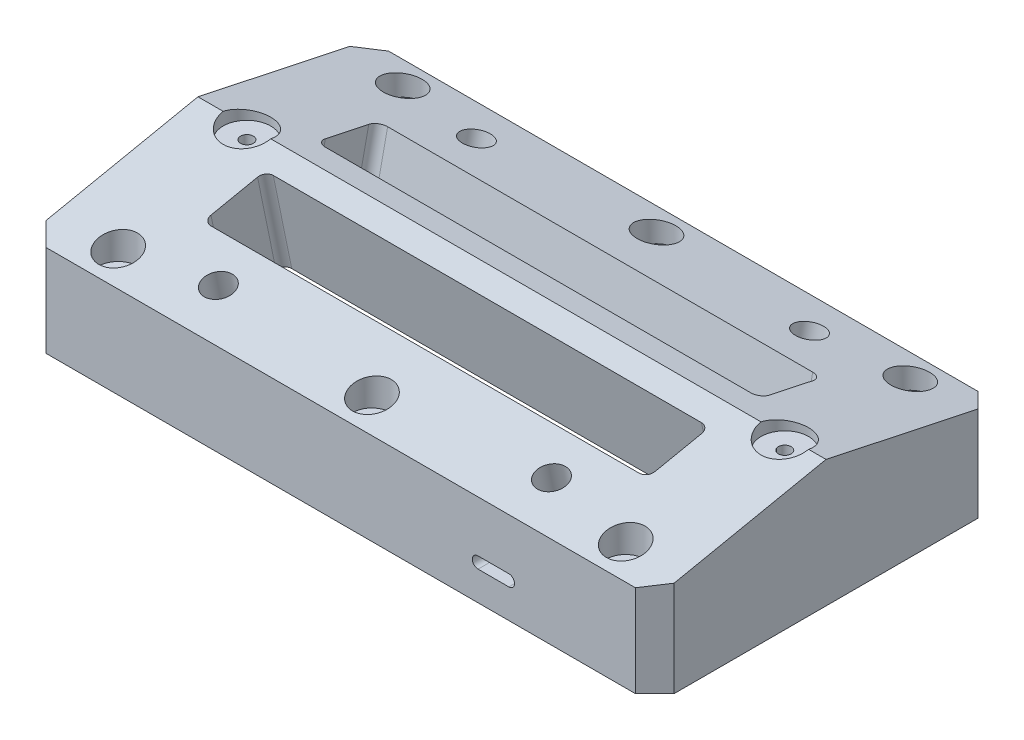
SolidWorks part; units mm, degrees
material "Custom Plastic"
ref_plane "Front Plane" through (0, 0, 0) normal (0, 0, 1) x (1, 0, 0)
ref_plane "Top Plane" through (0, 0, 0) normal (0, 1, 0) x (1, 0, 0)
ref_plane "Right Plane" through (0, 0, 0) normal (1, 0, 0) x (0, 0, -1)
sketch "Sketch1" plane through (0, 0, 0) normal (0, 1, 0) x (1, 0, 0)
  line L1 (0, 0) -> (198, 0)
  line L2 (0, 0) -> (0, 108)
  line L3 (0, 108) -> (198, 108)
  line L4 (198, 0) -> (198, 108)
  dimension "D1" = 198
  dimension "D2" = 108
extrude "Boss-Extrude1" add sketch "Sketch1" along normal blind 40
ref_plane "Left" through (198, 0, 0) normal (1, 0, 0) x (0, 0, -1)
ref_plane "Bot" through (0, 40, 0) normal (0, 1, 0) x (1, 0, 0)
ref_plane "der loco" through (0, 0, -52) normal (0, 0, -1) x (-1, 0, 0)
sketch "Sketch4" plane through (0, 0, 0) normal (0, 1, 0) x (1, 0, 0)
  line L0 (0, 108) -> (0, 0) construction
  line L1 (8.5, 31.5) -> (189.5, 31.5)
  line L2 (8.5, 31.5) -> (8.5, 76.5)
  line L3 (8.5, 76.5) -> (189.5, 76.5)
  line L4 (189.5, 31.5) -> (189.5, 76.5)
  line L5 (0, 0) -> (198, 0) construction
  dimension "D1" = 181
  dimension "D2" = 8.5
  dimension "D3" = 45
  dimension "D4" = 31.5
extrude "Cut-Extrude2" cut sketch "Sketch4" along normal blind 10 contours L2 L1 L4 L3
ref_plane "Plane32" through (0, 10, 0) normal (0, -1, 0) x (-1, 0, 0)
sketch "Sketch5" plane through (198, 0, 0) normal (1, 0, 0) x (0, 0, -1)
  line L0 (54, 40) -> (108, 28.5219)
  line L1 (0, 40) -> (108, 40) construction
  line L2 (108, 28.5219) -> (108, 40)
  line L3 (108, 40) -> (54, 40)
  line L4 (108, 40) -> (108, 0) construction
  dimension "D1" = 12
  dimension "D2" = 54
extrude "Cut-Extrude3" cut sketch "Sketch5" against normal blind 175
ref_plane "Plane24" through (0, 10, 0) normal (0, -1, 0) x (-1, 0, 0)
sketch "Sketch53" plane through (0, 10, 0) normal (0, -1, 0) x (-1, 0, 0)
  line L0 (-8.5, 51.5) -> (-8.5, 31.5)
  line L1 (-8.5, 76.5) -> (-8.5, 31.5) construction
  line L2 (-8.5, 31.5) -> (-39.5, 31.5)
  line L3 (-8.5, 31.5) -> (-189.5, 31.5) construction
  line L4 (-39.5, 31.5) -> (-8.5, 51.5)
  line L5 (-8.5, 54) -> (-189.5, 54) construction
  line L6 (-189.5, 31.5) -> (-189.5, 76.5) construction
  line L7 (-8.5, 56.5) -> (-8.5, 76.5)
  line L8 (-8.5, 76.5) -> (-39.5, 76.5)
  line L9 (-39.5, 76.5) -> (-8.5, 56.5)
  line L10 (-99, 76.5) -> (-99, 31.5) construction
  line L11 (-8.5, 76.5) -> (-189.5, 76.5) construction
  line L12 (-8.5, 31.5) -> (-189.5, 31.5) construction
  line L13 (-158.5, 76.5) -> (-189.5, 56.5)
  line L14 (-189.5, 76.5) -> (-158.5, 76.5)
  line L15 (-189.5, 56.5) -> (-189.5, 76.5)
  line L16 (-158.5, 31.5) -> (-189.5, 51.5)
  line L17 (-189.5, 31.5) -> (-158.5, 31.5)
  line L18 (-189.5, 51.5) -> (-189.5, 31.5)
  dimension "D1" = 31
  dimension "D2" = 20
extrude "Boss-Extrude11" add sketch "Sketch53" along normal up to surface (10 mm away) up to face at (99, 0, -54)
ref_plane "izq loco" through (0, 0, -57) normal (0, 0, -1) x (-1, 0, 0)
sketch "Sketch18" plane through (198, 0, 0) normal (1, 0, 0) x (0, 0, -1)
  line L0 (0, 28.9154) -> (0, 40)
  line L1 (0, 40) -> (0, 0) construction
  line L2 (0, 40) -> (54, 40)
  line L3 (54, 40) -> (0, 28.9154)
  line L4 (0, 40) -> (54, 40) construction
  line L5 (40.01, 37.1283) -> (56.6571, -43.9699) construction
  line L6 (54, -44.525) -> (24.4749, -50.6931) construction
  line L7 (0, 28.9154) -> (54, 28.9154) construction
  line L8 (54, 28.9154) -> (54, 40) construction
  line L9 (54, 28.9154) -> (108, 28.9154) construction
  line L10 (108, 28.5219) -> (108, 0) construction
  dimension "D1" = 54
  dimension "D2" = 11.6
  dimension "D3" = 13.99
  dimension "D4" = 11.6
extrude "Cut-Extrude12" cut sketch "Sketch18" against normal up to surface (175 mm away) up to face at (23, 36.174, -90)
sketch "Sketch60" plane through (0, 0, 0) normal (0, 1, 0) x (1, 0, 0)
  point P0 (8.5, 31.5)
  point P1 (39.5, 31.5)
  point P2 (8.5, 76.5)
  point P6 (39.5, 76.5)
  dimension "D1" = 20
  dimension "D2" = 31
  dimension "D3" = 20
  dimension "D4" = 31
ref_axis "Axis6" through (8.5, 0, -31.5) along (1, 0, 0)
sketch "Sketch69" plane through (0, 10, 0) normal (0, -1, 0) x (-1, 0, 0)
  point P0 (-39.5, 56.5)
  point P1 (-8.5, 51.5)
  point P2 (-38.5, 51.5)
  point P3 (-8.5, 56.5)
  dimension "D1" = 31
  dimension "D2" = 20
  dimension "D3" = 20
  dimension "D4" = 30
sketch "der loco axis" plane through (0, 0, -52) normal (0, 0, -1) x (-1, 0, 0)
  point P0 (-8.5, 8.5)
  point P1 (-38.5, 8.5)
  dimension "D1" = 1.5
sketch "izq loco axis" plane through (0, 0, -57) normal (0, 0, -1) x (-1, 0, 0)
  line L0 (-39.5, 0) -> (-39.5, 10) construction
  line L1 (-8.5, 0) -> (-8.5, 10) construction
  point P0 (-8.5, 8.4959)
  point P1 (-39.5, 8.4959)
  dimension "D1" = 1.5041
ref_plane "Plane3" through (0, 49.2528, -10.469) normal (0, 0.9781, -0.2079) x (1, 0, 0)
ref_axis "Axis8" through (39.5, 0, -76.5) along (-1, 0, 0)
ref_axis "Axis9" through (8.5, 8.4959, -57) along (1, 0, 0)
ref_axis "Axis10" through (38.5, 8.5, -52) along (-1, 0, 0)
ref_plane "Izq bueno" through (0, 28.0127, -12.2048) normal (0, 0.9168, -0.3994) x (1, 0, 0)
sketch "Izq" plane through (0, 28.0127, -12.2048) normal (0, 0.9168, -0.3994) x (1, 0, 0)
  line L0 (8.5, 48.8622) -> (29.5, 70.1326)
  line L1 (29.5, 70.1326) -> (8.5, 70.1326)
  line L2 (8.5, 70.1326) -> (8.5, 48.8622)
  dimension "D1" = 21
extrude "Cut-Extrude28" cut sketch "Izq" against normal blind 14.5
ref_plane "Der bueno" through (0, -11.1449, -4.6211) normal (0, 0.9237, 0.383) x (1, 0, 0)
sketch "Der" plane through (0, -11.1449, -4.6211) normal (0, 0.9237, 0.383) x (1, 0, 0)
  line L0 (8.5, 51.2902) -> (29.5, 29.0979)
  line L1 (29.5, 29.0979) -> (8.5, 29.0979)
  line L2 (8.5, 29.0979) -> (8.5, 51.2902)
  dimension "D1" = 21
extrude "Cut-Extrude29" cut sketch "Der" against normal blind 14.5
sketch "Sketch97" plane through (0, 0, 0) normal (0, 1, 0) x (1, 0, 0)
  line L0 (8.5, 57.5) -> (29.5, 76.5)
  line L1 (29.5, 76.5) -> (158.5, 76.5)
  line L3 (158.5, 31.5) -> (29.5, 31.5)
  line L4 (29.5, 31.5) -> (8.5, 51.5)
  line L5 (8.5, 51.5) -> (8.5, 57.5)
  line L7 (158.5, 76.5) -> (189.5, 56.5)
  line L8 (189.5, 56.5) -> (189.5, 51.5)
  line L9 (189.5, 51.5) -> (158.5, 31.5)
  line L10 (39.5, 76.5) -> (158.5, 76.5) construction
  dimension "D1" = 6
extrude "Cut-Extrude40" cut sketch "Sketch97" along normal up to surface (10 mm away) up to face at (99, 10, -54)
ref_axis "Axis11" through (99, 0, -108) along (0, 0, 1)
ref_plane "Plane33" through (99, 0, 0) normal (1, 0, 0) x (0, 0, -1)
mirror "Mirror2" about plane through (99, 0, 0) normal (1, 0, 0) of "Cut-Extrude29", "Cut-Extrude40", "Cut-Extrude28"
sketch "Sketch6" plane through (0, 49.2528, -10.469) normal (0, 0.9781, -0.2079) x (1, 0, 0)
  line L1 (32.2, 72.7099) -> (166.2, 72.7099)
  line L2 (29.2, 69.7099) -> (29.2, 55.7099)
  line L3 (32.2, 52.7099) -> (166.2, 52.7099)
  line L4 (169.2, 69.7099) -> (169.2, 55.7099)
  line L6 (23, 99.7099) -> (198, 99.7099) construction
  line L13 (198, 44.5035) -> (198, 99.7099) construction
  arc A0 (166.2, 72.7099) -> (169.2, 69.7099) centre (166.2, 69.7099) cw
  arc A1 (166.2, 52.7099) -> (169.2, 55.7099) centre (166.2, 55.7099) ccw
  arc A2 (29.2, 55.7099) -> (32.2, 52.7099) centre (32.2, 55.7099) ccw
  arc A3 (32.2, 72.7099) -> (29.2, 69.7099) centre (32.2, 69.7099) ccw
  point P14 (0, 0)
  point P15 (0, 0)
  point P18 (0, 0)
  dimension "D1" = 3
  dimension "D5" = 27
  dimension "D2" = 140
  dimension "D3" = 20
  dimension "D4" = 28.8
sketch "Sketch7" plane through (0, 0, 0) normal (1, 0, 0) x (0, 0, -1)
  line L1 (108, 40) -> (108, 0) construction
  line L2 (108, 40) -> (0, 40) construction
  line L3 (108, 40) -> (108, 35)
  line L5 (108, 35) -> (83.5051, 40)
  line L6 (108, 40) -> (83.5051, 40)
  line L7 (0, 35) -> (0, 40)
  line L8 (0, 40) -> (0, 0) construction
  line L9 (0, 40) -> (24.4949, 40)
  line L10 (24.4949, 40) -> (0, 35)
  dimension "D1" = 25
  dimension "D2" = 35
  dimension "D3" = 35
  dimension "D4" = 25
extrude "Cut-Extrude5" cut sketch "Sketch7" along normal up to vertex (23 mm away) up to point (23, 40, 0)
sketch "Sketch9" plane through (0, 40, 0) normal (0, 1, 0) x (1, 0, 0)
  line L0 (0, 83.5051) -> (0, 24.4949) construction
  circle A0 centre (15.45, 54) radius 8
  point P6 (0, 54)
  dimension "D1" = 16
  dimension "D2" = 15.45
sketch "Sketch12" plane through (0, 40, 0) normal (0, 1, 0) x (1, 0, 0)
  line L0 (0, 83.5051) -> (0, 108) construction
  line L2 (23, 108) -> (0, 108) construction
  line L3 (23, 0) -> (0, 0) construction
  circle A0 centre (19.7, 98.85) radius 3.15
  circle A1 centre (99.7, 9.15) radius 3.15
  circle A2 centre (179.7, 9.15) radius 3.15
  circle A3 centre (19.7, 9.15) radius 3.15
  circle A4 centre (99.7, 98.85) radius 3.15
  circle A5 centre (179.7, 98.85) radius 3.15
  dimension "D2" = 6.3
  dimension "D3" = 19.7
  dimension "D7" = 80
  dimension "D9" = 80
  dimension "D10" = 9.15
  dimension "D11" = 9.15
extrude "Cut-Extrude9" cut sketch "Sketch12" against normal through all
sketch "Sketch13" plane through (0, 49.2528, -10.469) normal (0, 0.9781, -0.2079) x (1, 0, 0)
  line L0 (23, 44.5035) -> (23, 99.7099) construction
  line L1 (23, 99.7099) -> (198, 99.7099) construction
  line L2 (198, 44.5035) -> (198, 99.7099) construction
  circle A0 centre (46.5, 86.7099) radius 4.5
  circle A1 centre (151.5, 86.7099) radius 4.5
  dimension "D1" = 9
  dimension "D4" = 9
  dimension "D2" = 23.5
  dimension "D3" = 13
  dimension "D5" = 46.5
extrude "Cut-Extrude10" cut sketch "Sketch13" against normal blind 16.5
ref_plane "Plane8" through (0, 33.6, 6.8586) normal (0, 0.9798, 0.2) x (1, 0, 0)
sketch "Sketch14" plane through (0, 27.1558, 8.572) normal (0, 0.9796, 0.2011) x (1, 0, 0)
  line L0 (23, 9.9742) -> (0, 9.9742) construction
  line L1 (23, 63.8767) -> (23, 114.4658) construction
  line L2 (198, 9.9742) -> (198, 34.9742) construction
  circle A0 centre (46.5, 22.9742) radius 4.5
  circle A1 centre (151.5, 22.9742) radius 4.5
  dimension "D1" = 9
  dimension "D2" = 9
  dimension "D3" = 13
  dimension "D4" = 23.5
  dimension "D5" = 46.5
extrude "Cut-Extrude11" cut sketch "Sketch14" against normal blind 16.5
ref_plane "Plane9" through (0, 27.7463, 5.6955) normal (0, 0.9796, 0.2011) x (1, 0, 0)
sketch "Sketch23" plane through (0, 27.7463, 5.6955) normal (0, 0.9796, 0.2011) x (1, 0, 0)
  line L0 (23, 60.9402) -> (198, 60.9402) construction
  line L1 (28.9, 60.1402) -> (169.5, 60.1402)
  line L2 (25.9, 57.1402) -> (25.9, 36.5402)
  line L3 (28.9, 33.5402) -> (169.5, 33.5402)
  line L4 (172.5, 57.1402) -> (172.5, 36.5402)
  line L7 (28.6, 57.4402) -> (169.8, 57.4402)
  line L8 (28.6, 57.4402) -> (28.6, 36.2402)
  line L9 (28.6, 36.2402) -> (169.8, 36.2402)
  line L10 (169.8, 57.4402) -> (169.8, 36.2402)
  line L12 (198, 5.8142) -> (198, 60.9402) construction
  arc A0 (169.5, 60.1402) -> (172.5, 57.1402) centre (169.5, 57.1402) cw
  arc A1 (169.5, 33.5402) -> (172.5, 36.5402) centre (169.5, 36.5402) ccw
  arc A2 (25.9, 36.5402) -> (28.9, 33.5402) centre (28.9, 36.5402) ccw
  arc A3 (28.9, 60.1402) -> (25.9, 57.1402) centre (28.9, 57.1402) ccw
  point P10 (172.5, 60.1402)
  point P15 (25.9, 33.5402)
  point P18 (25.9, 60.1402)
  dimension "D5" = 3
  dimension "D1" = 146.6
  dimension "D2" = 20.6
  dimension "D3" = 3.5
  dimension "D4" = 25.5
  dimension "D6" = 2.7
  dimension "D7" = 2.7
  dimension "D8" = 2.7
  dimension "D9" = 2.7
sketch "Sketch41" plane through (0, 0, 0) normal (0, 1, 0) x (1, 0, 0)
  line L0 (198, 0) -> (198, 108) construction
  line L1 (198, 108) -> (0, 108) construction
  line L2 (0, 0) -> (198, 0) construction
  circle A0 centre (139.5, 9) radius 2.9
  circle A1 centre (139.5, 99) radius 2.9
  dimension "D1" = 5.8
  dimension "D4" = 5.8
  dimension "D2" = 58.5
  dimension "D3" = 58.5
  dimension "D5" = 9
  dimension "D6" = 9
extrude "Cut-Extrude21" cut sketch "Sketch41" along normal blind 7
sketch "Sketch42" plane through (0, 0, 0) normal (0, 0, 1) x (1, 0, 0)
  line L0 (198, 28.9154) -> (198, 0) construction
  line L5 (0, 0) -> (198, 0) construction
  line L6 (142.3, 12.8) -> (152, 12.8)
  line L7 (142.3, 9.2) -> (152, 9.2)
  arc A0 (142.3, 12.8) -> (142.3, 9.2) centre (142.3, 11) ccw
  arc A2 (152, 12.8) -> (152, 9.2) centre (152, 11) cw
  dimension "D2" = 1.8
  dimension "D3" = 1.8
  dimension "D1" = 9.7
  dimension "D5" = 46
  dimension "D6" = 11
extrude "Cut-Extrude22" cut sketch "Sketch42" against normal blind 10
ref_plane "Plane19" through (0, 0, -108) normal (0, 0, -1) x (-1, 0, 0)
sketch "Sketch43" plane through (0, 0, -108) normal (0, 0, -1) x (-1, 0, 0)
  line L0 (-55.7, 11) -> (-46, 11) construction
  line L1 (-55.7, 12.8) -> (-46, 12.8)
  line L2 (-55.7, 9.2) -> (-46, 9.2)
  line L3 (-198, 0) -> (0, 0) construction
  line L4 (0, 35) -> (0, 0) construction
  arc A0 (-55.7, 12.8) -> (-55.7, 9.2) centre (-55.7, 11) ccw
  arc A1 (-46, 9.2) -> (-46, 12.8) centre (-46, 11) ccw
  point P2 (-50.85, 11)
  dimension "D2" = 1.8
  dimension "D1" = 9.7
  dimension "D3" = 11
  dimension "D4" = 46
extrude "Cut-Extrude23" cut sketch "Sketch43" against normal blind 10
extrude "Cut-Extrude32" cut sketch "Sketch6" against normal blind 43.3
sketch "Sketch83" plane through (0, 27.7463, 5.6955) normal (0, 0.9796, 0.2011) x (1, 0, 0)
  line L1 (31.7, 52.8142) -> (166.7, 52.8142)
  line L2 (29.2, 50.3142) -> (29.2, 35.3142)
  line L3 (31.7, 32.8142) -> (166.7, 32.8142)
  line L4 (169.2, 50.3142) -> (169.2, 35.3142)
  line L7 (198, 5.8142) -> (198, 60.9402) construction
  line L8 (23, 5.8142) -> (198, 5.8142) construction
  arc A0 (166.7, 32.8142) -> (169.2, 35.3142) centre (166.7, 35.3142) ccw
  arc A1 (166.7, 52.8142) -> (169.2, 50.3142) centre (166.7, 50.3142) cw
  arc A2 (29.2, 35.3142) -> (31.7, 32.8142) centre (31.7, 35.3142) ccw
  arc A3 (31.7, 52.8142) -> (29.2, 50.3142) centre (31.7, 50.3142) ccw
  point P12 (169.2, 52.8142)
  point P15 (29.2, 32.8142)
  point P18 (29.2, 52.8142)
  point P19 (169.2, 42.8142)
  dimension "D5" = 2.5
  dimension "D1" = 140
  dimension "D2" = 20
  dimension "D3" = 27
  dimension "D4" = 28.8
extrude "Cut-Extrude34" cut sketch "Sketch83" against normal blind 55.4
sketch "Sketch84" plane through (0, 49.2528, -10.469) normal (0, 0.9781, -0.2079) x (1, 0, 0)
  line L1 (35.5601, 49.4099) -> (170.5601, 49.4099)
  line L2 (33.0601, 51.9099) -> (33.0601, 66.9099)
  line L3 (35.5601, 69.4099) -> (170.5601, 69.4099)
  line L4 (173.0601, 51.9099) -> (173.0601, 66.9099)
  line L7 (29.2, 69.7099) -> (29.2, 55.7099) construction
  line L11 (166.2, 72.7099) -> (32.2, 72.7099) construction
  arc A0 (170.5601, 49.4099) -> (173.0601, 51.9099) centre (170.5601, 51.9099) ccw
  arc A1 (170.5601, 69.4099) -> (173.0601, 66.9099) centre (170.5601, 66.9099) cw
  arc A2 (33.0601, 66.9099) -> (35.5601, 69.4099) centre (35.5601, 66.9099) cw
  arc A3 (35.5601, 49.4099) -> (33.0601, 51.9099) centre (35.5601, 51.9099) cw
  point P10 (173.0601, 49.4099)
  point P13 (173.0601, 69.4099)
  point P16 (33.0601, 69.4099)
  point P19 (173.0601, 59.4099)
  dimension "D5" = 2.5
  dimension "D1" = 140
  dimension "D2" = 20
  dimension "D3" = 3.3
  dimension "D4" = 3.8601
extrude "Cut-Extrude35" [suppressed] cut sketch "Sketch84" against normal blind 55.4
sketch "Sketch85" plane through (0, 40, 0) normal (0, 1, 0) x (1, 0, 0)
  line L0 (0, 101.9) -> (6.1, 108)
  line L1 (0, 83.5051) -> (0, 108) construction
  line L2 (23, 108) -> (0, 108) construction
  line L3 (6.1, 108) -> (0, 108)
  line L4 (0, 108) -> (0, 101.9)
  line L5 (0, 0) -> (6.1, 0)
  line L6 (23, 0) -> (0, 0) construction
  line L7 (6.1, 0) -> (0, 6.1)
  line L8 (0, 0) -> (0, 24.4949) construction
  line L9 (0, 6.1) -> (0, 0)
  line L10 (198, 6.1) -> (191.9, 0)
  line L11 (198, 0) -> (198, 54) construction
  line L12 (23, 0) -> (198, 0) construction
  line L13 (191.9, 0) -> (198, 0)
  line L14 (198, 0) -> (198, 6.1)
  line L15 (198, 108) -> (191.9, 108)
  line L16 (23, 108) -> (198, 108) construction
  line L17 (191.9, 108) -> (198, 101.9)
  line L18 (198, 54) -> (198, 108) construction
  line L19 (198, 101.9) -> (198, 108)
  dimension "D1" = 6.1
  dimension "D2" = 6.1
  dimension "D3" = 6.1
  dimension "D4" = 6.1
  dimension "D5" = 6.1
  dimension "D6" = 6.1
  dimension "D7" = 6.1
extrude "Cut-Extrude36" cut sketch "Sketch85" against normal blind 55.4
sketch "Sketch90" plane through (0, 40, 0) normal (0, 1, 0) x (1, 0, 0)
  circle A0 centre (19.7, 9.15) radius 6.1
  circle A1 centre (99.7, 9.15) radius 6.1
  circle A2 centre (179.7, 9.15) radius 6.1
  circle A3 centre (99.7, 98.85) radius 6.1
  circle A4 centre (179.7, 98.85) radius 6.1
  circle A5 centre (19.7, 98.85) radius 6.1
  circle A6 centre (179.7, 98.85) radius 3.15 construction
  circle A7 centre (99.7, 98.85) radius 3.15 construction
  dimension "D1" = 12.2
  dimension "D2" = 3
  dimension "D3" = 2
extrude "Cut-Extrude38" cut sketch "Sketch90" against normal blind 17
sketch "Sketch96" plane through (0, 0, 0) normal (0, 1, 0) x (1, 0, 0)
  line L0 (23, 54) -> (198, 54) construction
  line L1 (198, 6.1) -> (198, 101.9) construction
  circle A0 centre (15.45, 54) radius 2
  circle A1 centre (185, 54) radius 2
  dimension "D1" = 4
  dimension "D2" = 4
  dimension "D3" = 13
extrude "Cut-Extrude39" cut sketch "Sketch96" along normal through all
sketch "Sketch98" plane through (0, 40, 0) normal (0, 1, 0) x (1, 0, 0)
  circle A0 centre (185, 54) radius 7.5
  circle A1 centre (15.45, 54) radius 7.5
  dimension "D1" = 15
  dimension "D2" = 15
extrude "Cut-Extrude41" cut sketch "Sketch98" against normal blind 4
sketch "Sketch99" plane through (198, 0, 0) normal (1, 0, 0) x (0, 0, -1)
  line L1 (71.8085, 36.2147) -> (54, -44.525) construction
  line L2 (54, -44.525) -> (83.5034, -50.7961) construction
  line L4 (54, 40) -> (108, 28.5219) construction
  line L5 (6.1, 30.1675) -> (54, 40) construction
  line L6 (36.2443, 36.3553) -> (54, -44.525)
  line L8 (78.6556, 34.7593) -> (64.9615, 37.6701) construction
  line L9 (28.8975, 34.8472) -> (43.5911, 37.8634) construction
  line L10 (54, -44.525) -> (24.4536, -50.59) construction
  circle A1 centre (54, -44.525) radius 30.1625
  point P1 (20.7236, -44.525)
  point P6 (53.5184, -41.8236)
  point P7 (0, 0)
  point P13 (0, 0)
  point P15 (71.8085, 36.2147)
  point P19 (36.2443, 36.3553)
  point P20 (83.5034, -50.59)
  dimension "D1" = 89.562
  dimension "D7" = 60.325
  dimension "D2" = 89.218
  dimension "D6" = 44.525
sketch "Sketch100" plane through (198, 0, 0) normal (1, 0, 0) x (0, 0, -1)
  line L0 (16, 40) -> (16, 32.1997)
  line L1 (6.1, 30.1675) -> (54, 40) construction
  line L2 (16, 32.1997) -> (54, 40)
  line L3 (54, 40) -> (93.7197, 31.5573) construction
  line L4 (54, 40) -> (16, 40)
  dimension "D1" = 16
extrude "Cut-Extrude42" [suppressed] cut sketch "Sketch100" against normal blind 175
sketch "Sketch101" plane through (198, 0, 0) normal (1, 0, 0) x (0, 0, -1)
  line L0 (54, 40) -> (83.5051, 40)
  line L1 (83.5051, 40) -> (83.5051, 33.7285)
  line L2 (103.9803, 29.3764) -> (108, 28.5219) construction
  line L3 (83.5051, 33.7285) -> (54, 40)
extrude "Cut-Extrude43" [suppressed] cut sketch "Sketch101" against normal blind 175
sketch "Croquis1" plane through (0, 0, 0) normal (1, 0, 0) x (0, 0, -1)
  line L0 (108, 40) -> (108, 28.5219)
  line L1 (108, 28.5219) -> (54, 40)
  line L2 (54, 40) -> (108, 40)
extrude "Cortar-Extruir1" cut sketch "Croquis1" along normal up to vertex (23 mm away) up to point (23, 40, -54)
sketch "Croquis2" plane through (0, 0, 0) normal (1, 0, 0) x (0, 0, -1)
  line L0 (54, 40) -> (0, 40)
  line L1 (0, 40) -> (0, 28.9154)
  line L2 (0, 28.9154) -> (54, 40)
extrude "Cortar-Extruir2" cut sketch "Croquis2" along normal up to vertex (23 mm away) up to point (23, 35, 0)
